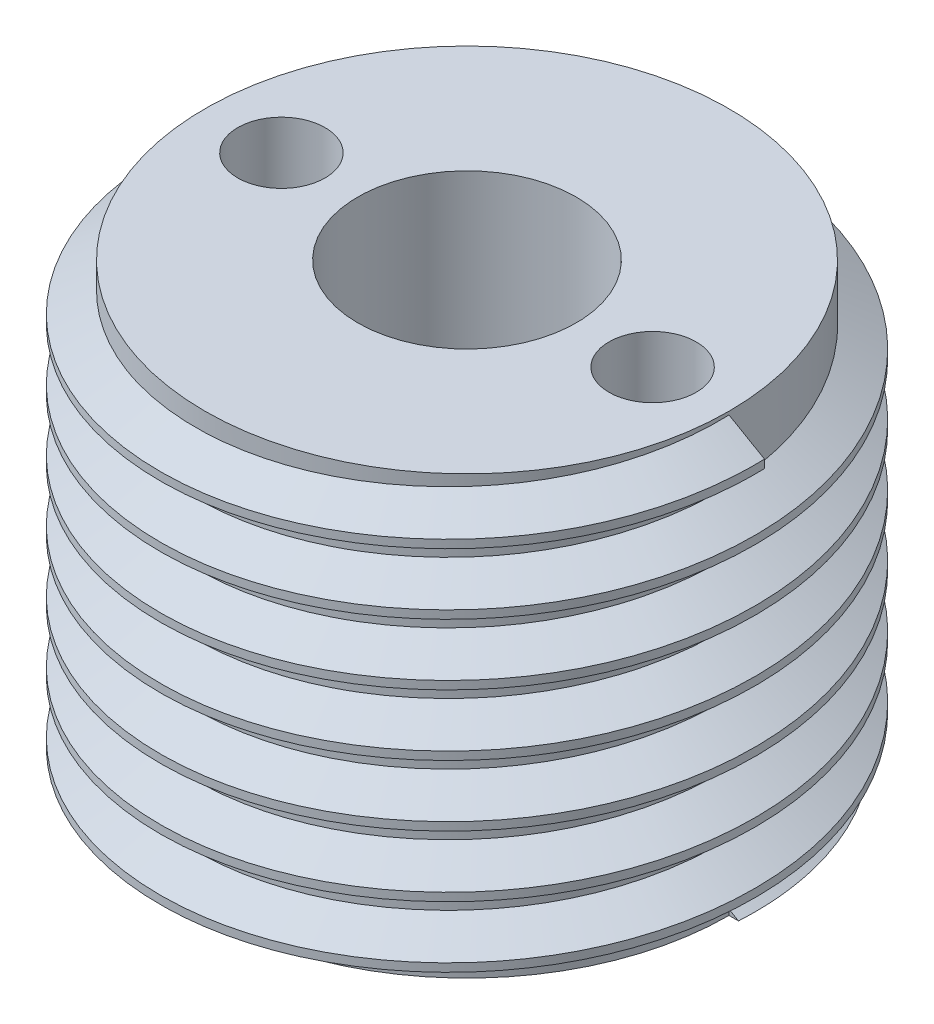
SolidWorks part; units mm, degrees
ref_plane "Plan de face" through (0, 0, 0) normal (0, 0, 1) x (1, 0, 0)
ref_plane "Plan de dessus" through (0, 0, 0) normal (0, 1, 0) x (1, 0, 0)
ref_plane "Plan de droite" through (0, 0, 0) normal (1, 0, 0) x (0, 0, -1)
sketch "Esquisse1" plane through (0, 0, 0) normal (0, 1, 0) x (1, 0, 0)
  circle A0 centre (0, 0) radius 6
  dimension "D1" = 12
extrude "Boss.-Extru.1" add sketch "Esquisse1" along normal blind 10
thread "Filetage1" pitch 1.5 method extrude trim with start face yes profile "Profil de filetage2" start angle 0, offset 1, length 0, pitch 1.4, diameter 12
ref_plane "Plan2" through (6, -1, 0) normal (0, 0, 1) x (1, 0, 0)
sketch "Profil de filetage2" plane through (6, -1, 0) normal (0, 0, 1) x (1, 0, 0)
  line L0 (0, 0) -> (0, 1.5) construction
  line L1 (0, 0) -> (0.8119, 0.4687)
  line L2 (0.8119, 0.4687) -> (0.8119, 0.6562)
  line L3 (0.8119, 0.6562) -> (0, 1.125)
  line L4 (0.8119, 0.5625) -> (0, 0.5625) construction
  line L11 (0, 0) -> (0, 1.125)
  point P2 (0, 0)
  dimension "Pitch" = 1.5
  dimension "Profile_Angle" = 60
  dimension "Profile_Land" = 0.1875
  dimension "Profile_Height" = 0.8119
sketch "Esquisse23" plane through (0, 10, 0) normal (0, 1, 0) x (1, 0, 0)
  circle A0 centre (0, 0) radius 2.5
  dimension "D1" = 5
extrude "Enlèv. mat.-Extru.1" cut sketch "Esquisse23" against normal blind 5.5
sketch "Esquisse24" plane through (0, 10, 0) normal (0, 1, 0) x (1, 0, 0)
  line L0 (0, 0) -> (1.9932, 0) construction
  line L1 (0, 0) -> (0, -1.7744) construction
  circle A0 centre (4.25, 0) radius 1
  circle A3 centre (-4.25, 0) radius 1
  point P4 (0, 0)
  dimension "D2" = 2
  dimension "D1" = 8.5
extrude "Enlèv. mat.-Extru.2" cut sketch "Esquisse24" against normal blind 3
